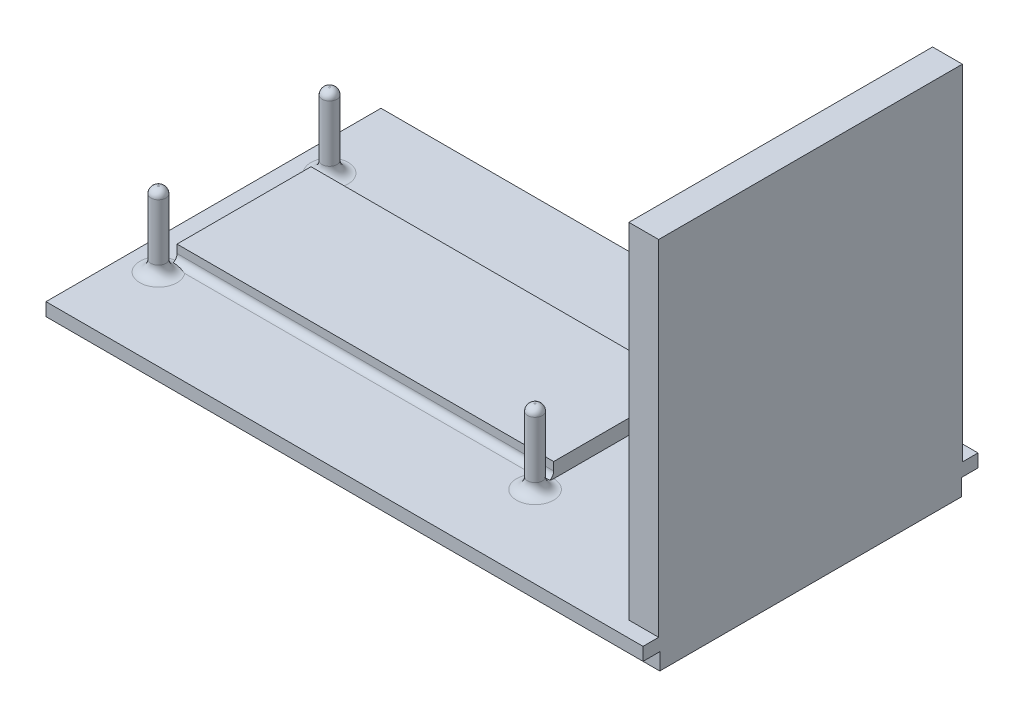
SolidWorks part; units mm, degrees
other "Marquage1"
sketch "Esquisse8" plane through (0, 4, 0) normal (-0.1599, 0.1072, 0.9813) x (0.7503, 0.6592, 0.0503)
ref_plane "Plan de face" through (0, 0, 0) normal (0, 0, 1) x (1, 0, 0)
ref_plane "Plan de dessus" through (0, 0, 0) normal (0, 1, 0) x (1, 0, 0)
ref_plane "Plan de droite" through (0, 0, 0) normal (1, 0, 0) x (0, 0, -1)
sketch "Esquisse9" plane through (0, 0, 0) normal (1, 0, 0) x (0, 0, -1)
  line L1 (0, 0) -> (45, 0)
  line L2 (0, 0) -> (0, 4)
  line L3 (0, 4) -> (45, 4)
  line L4 (45, 0) -> (45, 4)
  line L5 (0, 0) -> (2.25, 0)
  line L6 (0, 0) -> (0, 2.25)
  line L7 (45, 0) -> (42.75, 0)
  line L8 (45, 0) -> (45, 2.25)
  line L9 (45, 2.25) -> (42.75, 2.25)
  line L10 (42.75, 0) -> (42.75, 2.25)
  line L11 (0, 2.25) -> (2.25, 2.25)
  line L12 (2.25, 0) -> (2.25, 2.25)
  dimension "D1" = 45
  dimension "D2" = 2.25
  dimension "D3" = 2.25
  dimension "D4" = 2.25
  dimension "D5" = 2.25
  dimension "D6" = 4
extrude "Boss.-Extru.4" add sketch "Esquisse9" along normal blind 80.2 contours L1 L10 L9 L4 L3 L2 L11 region at (0, 2.0522, -22.5)
sketch "Esquisse10" plane through (0, 0, -2.25) normal (0, 0, 1) x (1, 0, 0)
  line L0 (80.2, 2.25) -> (0, 2.25) construction
  line L1 (0, 0) -> (2.1, 0)
  line L2 (0, 0) -> (0, 2.25)
  line L3 (0, 2.25) -> (2.1, 2.25)
  line L4 (2.1, 0) -> (2.1, 2.25)
  dimension "D1" = 2.1
extrude "Enlèv. mat.-Extru.5" cut sketch "Esquisse10" against normal through all both and the other way through all
sketch "Esquisse11" plane through (80.2, 0, 0) normal (1, 0, 0) x (0, 0, -1)
  line L0 (0, 4) -> (45, 4) construction
  line L1 (2.1, 4) -> (42.9, 4)
  line L2 (2.1, 4) -> (2.1, 49.5)
  line L3 (2.1, 49.5) -> (42.9, 49.5)
  line L4 (42.9, 4) -> (42.9, 49.5)
  dimension "D1" = 45.5
  dimension "D2" = 2.1
  dimension "D3" = 2.1
extrude "Boss.-Extru.5" add sketch "Esquisse11" against normal blind 4
sketch "Esquisse12" plane through (0, 49.5, 0) normal (0, 1, 0) x (1, 0, 0)
  line L1 (76.2, 42.9) -> (80.2, 42.9)
  line L2 (76.2, 42.9) -> (76.2, 2.1)
  line L3 (76.2, 2.1) -> (80.2, 2.1)
  line L4 (80.2, 42.9) -> (80.2, 2.1)
extrude "Boss.-Extru.6" add sketch "Esquisse12" along normal blind 0.78
sketch "Esquisse13" plane through (0, 4, 0) normal (0, 1, 0) x (1, 0, 0)
  line L1 (80.2, 45) -> (0, 45) construction
  line L2 (2.1, 42.75) -> (2.1, 2.25) construction
  line L3 (80.2, 0) -> (0, 0) construction
  circle A0 centre (4.1, 34) radius 1
  circle A1 centre (4.1, 11) radius 1
  circle A2 centre (54.7, 11) radius 1
  circle A3 centre (54.7, 34) radius 1
  dimension "D2" = 2
  dimension "D3" = 2
  dimension "D4" = 2
  dimension "D5" = 2
  dimension "D13" = 11
  dimension "D6" = 23
  dimension "D7" = 23
  dimension "D8" = 50.6
  dimension "D9" = 50.6
  dimension "D10" = 11
  dimension "D11" = 2
  dimension "D12" = 11
extrude "Boss.-Extru.7" add sketch "Esquisse13" along normal blind 10
fillet "Congé1" radius 1.5 4 edges at (4.1, 4, -33) (54.7, 4, -33) (54.7, 4, -10) (4.1, 4, -10)
fillet "Congé5" radius 0.9 4 edges at (54.7, 14, -10) (54.7, 14, -33) (4.1, 14, -33) (4.1, 14, -10)
sketch "Esquisse14" plane through (0, 4, 0) normal (0, 1, 0) x (1, 0, 0)
  line L1 (4.1, 31.5) -> (54.7, 31.5)
  line L2 (4.1, 31.5) -> (4.1, 13.5)
  line L3 (4.1, 13.5) -> (54.7, 13.5)
  line L4 (54.7, 31.5) -> (54.7, 13.5)
  circle A0 centre (4.1, 34) radius 2.5 construction
  circle A1 centre (54.7, 11) radius 2.5 construction
extrude "Boss.-Extru.8" add sketch "Esquisse14" along normal blind 2
fillet "Congé7" radius 0.9 2 edges at (29.4, 4, -31.5) (29.4, 4, -13.5)
